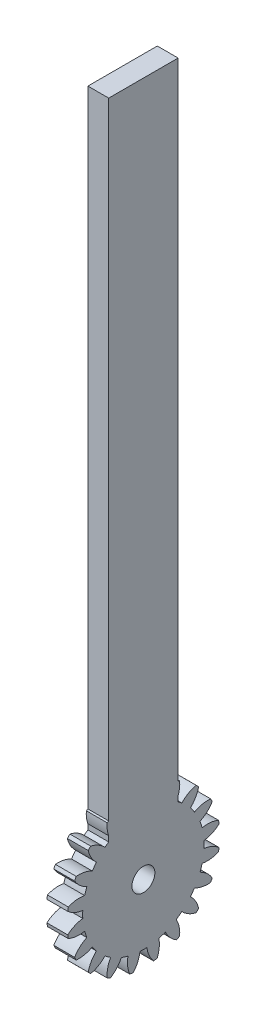
SolidWorks part; units mm, degrees
ref_plane "Plane1" through (0, 0, 0) normal (0, 0, 1) x (1, 0, 0)
ref_plane "Plane2" through (0, 0, 0) normal (0, 1, 0) x (1, 0, 0)
ref_plane "Plane3" through (0, 0, 0) normal (1, 0, 0) x (0, 0, -1)
sketch "HoldingSke" plane through (0, 0, 0) normal (0, 1, 0) x (1, 0, 0)
  line L0 (0, 0) -> (0.9397, -0.342)
  line L1 (-15, 0) -> (100, 0) construction
  line L2 (0, 0) -> (-2.1039, 2.3779)
  line L3 (0, 0) -> (-11.863, 4.5341)
  line L4 (0, 0) -> (8.1152, 2.9537)
  line L5 (0, 0) -> (-46.8476, -17.4728)
  line L6 (0, 0) -> (-2.4869, -1.6779)
  line L7 (-2.1039, 2.3779) -> (8.6586, 51.2059)
  line L8 (-76.2, 54.61) -> (-75.3, 54.61)
  line L9 (-71.009, 38.7566) -> (-53.1078, 45.2721)
  line L10 (-76.2, 71.12) -> (104.1128, 71.12)
  line L11 (0, 0) -> (-3, 0)
  line L12 (-76.2, 101.6) -> (-76.162, 101.6)
  line L13 (24.9733, 27.94) -> (52.9518, 28.4284)
  line L14 (24.9733, 27.94) -> (24.9743, 27.94)
  line L15 (24.9733, 27.94) -> (100.4006, 29.5858)
  line L16 (-63.627, -1) -> (-12.827, -1)
  circle A0 centre (0, 0) radius 2.5
  circle A1 centre (0, 0) radius 8.749
  circle A2 centre (0, 0) radius 37.5
  circle A3 centre (0, 0) radius 2.5
  dimension "Num_teeth" = 20
  dimension "Pitch_radius" = 180.3128
  dimension "Width" = 3
  dimension "Thickness" = 3
sketch "BasProSke" plane through (0, 0, 0) normal (0, 1, 0) x (1, 0, 0)
  line L0 (-10, 0) -> (60, 0) construction
  line L1 (0, 0) -> (0, 11)
  line L2 (0, 0) -> (3, 0)
  line L3 (3, 0) -> (3, 11)
  line L4 (3, 11) -> (0, 11)
  dimension "Thickness" = 3
  dimension "Diameter" = 22
revolve "Base-Revolve" add sketch "BasProSke" angle 360 about L0
sketch "TooCutSke" plane through (0, 0, 0) normal (1, 0, 0) x (0, 0, -1)
  line L1 (0, 0) -> (0, 107) construction
  line L2 (0, 0) -> (-0.8511, 9.9637) construction
  line L3 (0, 0) -> (-3.1206, 19.7028) construction
  line L4 (-0.8511, 9.9637) -> (-1.5603, 9.8514) construction
  arc A0 (0.4999, 8.7347) -> (-0.4999, 8.7347) centre (0, 0) ccw
  arc A1 (1.4852, 10.9249) -> (-1.4852, 10.9249) centre (0, 0) ccw
  circle A2 centre (0, 0) radius 10 construction
  circle A3 centre (0, 0) radius 9.3969 construction
  arc A4 (-0.4999, 8.7347) -> (-1.4852, 10.9249) centre (-4.4722, 8.2645) ccw
  arc A5 (1.4852, 10.9249) -> (0.4999, 8.7347) centre (4.4722, 8.2645) ccw
extrude "ToothCut" cut sketch "TooCutSke" along normal through all
fillet "Breaks" [suppressed] radius 0.02 tangent propagation no
fillet "RootFillets" [suppressed] radius 0.251
pattern_circular "TeethCuts" count 20 every 18 about axis through (-10, 0, 0) along (1, 0, 0) of "ToothCut", "RootFillets", "Breaks"
sketch "HubNeaOneSke" plane through (0, 0, 0) normal (-1, 0, 0) x (0, 0, 1)
  circle A0 centre (0, 0) radius 8.749
  dimension "Diameter" = 17.498
extrude "HubNearOne" [suppressed] add sketch "HubNeaOneSke" along normal blind 47.0001
sketch "HubNeaBotSke" plane through (0, 0, 0) normal (-1, 0, 0) x (0, 0, 1)
  circle A0 centre (0, 0) radius 8.749
  dimension "Diameter" = 17.498
extrude "HubNearBoth" [suppressed] add sketch "HubNeaBotSke" along normal blind 23.5
ref_plane "FarPln" through (3, 0, 0) normal (1, 0, 0) x (0, 0, -1)
sketch "HubFarSke" plane through (3, 0, 0) normal (1, 0, 0) x (0, 0, -1)
  circle A0 centre (0, 0) radius 8.749
  dimension "Diameter" = 17.498
extrude "HubFar" [suppressed] add sketch "HubFarSke" along normal blind 23.5
sketch "BorSke" plane through (0, 0, 0) normal (1, 0, 0) x (0, 0, -1)
  circle A0 centre (0, 0) radius 2.5
  dimension "Diameter" = 5
extrude "Bore" cut sketch "BorSke" along normal mid plane 100.0001
sketch "KeySke" plane through (0, 0, 0) normal (1, 0, 0) x (0, 0, -1)
  line L0 (-1, 0) -> (-1, 3.4)
  line L1 (-1, 3.4) -> (1, 3.4)
  line L2 (1, 3.4) -> (1, 0)
  line L3 (0, 0) -> (0, 34) construction
  line L4 (-1, 0) -> (1, 0)
  dimension "Width" = 2
extrude "Keyway" [suppressed] cut sketch "KeySke" along normal mid plane 100.0001
pattern_circular "Keyway2" [suppressed] count 2 every 90 about axis through (-10, 0, 0) along (1, 0, 0) reverse direction yes
sketch "Sketch1" plane through (3, 0, 0) normal (1, 0, 0) x (0, 0, -1)
  line L1 (-5, 0) -> (5, 0)
  line L2 (-5, 0) -> (-5, 100)
  line L3 (-5, 100) -> (5, 100)
  line L4 (5, 0) -> (5, 100)
  dimension "D1" = 10
  dimension "D2" = 100
extrude "Boss-Extrude1" add sketch "Sketch1" against normal blind 3
sketch "Sketch5" plane through (3, 0, 0) normal (1, 0, 0) x (0, 0, -1)
  line L0 (-2.5, 0) -> (2.5, 0) construction
  line L1 (2.5, 0) -> (-2.5, 0)
  arc A0 (-2.5, 0) -> (2.5, 0) centre (0, 0) cw
extrude "Cut-Extrude2" cut sketch "Sketch5" against normal blind 3
sketch "Sketch6" plane through (3, 0, 0) normal (1, 0, 0) x (0, 0, -1)
  circle A0 centre (0, 0) radius 2.5
  circle A1 centre (0, 0) radius 1.65
extrude "Boss-Extrude2" add sketch "Sketch6" against normal blind 3
equation "' \"Module@HoldingSke\" = 6.35"
equation "' \"Num_teeth@HoldingSke\" = 12"
equation "' \"Ap@HoldingSke\" =  20"
equation "' \"Ap@HoldingSke\" = 20"
equation "' \"Width@HoldingSke\" = 0.5 * 25.4"
equation "' \"Hub_dia@HoldingSke\"= 1 * 25.4"
equation "' \"Hub_dia@HoldingSke\" = 1 * 25.4"
equation "' \"Overall_len@HoldingSke\" = 1.0 * 25.4"
equation "' \"Bore@HoldingSke\" = 0.75 * 25.4"
equation "' \"T_dim@HoldingSke\" = 0.1 * 25.4"
equation "' \"Width@KeySke\" = 0.25 * 25.4"
equation "' \"Show_teeth@HoldingSke\" = 13"
equation "' \"Backlash@HoldingSke\" = 0.009 * 25.4"
equation "' \"Addendum_fac@HoldingSke\" = 1.0"
equation "' \"Dedendum_fac@HoldingSke\" = 1.25"
equation "' \"Dedendum_add@HoldingSke\" = 0.00005 * 25.4"
equation "' \"Clearance_fac@HoldingSke\" = 0.25"
equation "\"Pitch@HoldingSke\" = 1 / \"Module@HoldingSke\""
equation "\"Overcut_dia@TooCutSke\" = (\"Num_teeth@HoldingSke\" + 2 * \"Addendum_fac@HoldingSke\") / \"Pitch@HoldingSke\" + 0.002 * 25.4"
equation "\"Pitch_dia@TooCutSke\" = \"Num_teeth@HoldingSke\" / \"Pitch@HoldingSke\""
equation "\"Base_dia@TooCutSke\" = \"Num_teeth@HoldingSke\" / \"Pitch@HoldingSke\" * cos((\"Ap@HoldingSke\"  * 3.14159265 / 180))"
equation "\"Root_dia@TooCutSke\" = (\"Num_teeth@HoldingSke\" + 2) / \"Pitch@HoldingSke\" - 2 * (\"Addendum_fac@HoldingSke\" + \"Dedendum_fac@HoldingSke\") / \"Pitch@HoldingSke\" - \"Dedendum_add@HoldingSke\" * 2"
equation "\"Half_ang@TooCutSke\" = 180 / \"Num_teeth@HoldingSke\""
equation "\"Half_CT@TooCutSke\" = \"Num_teeth@HoldingSke\" / \"Pitch@HoldingSke\" * sin((3.14159265 / 2 / \"Num_teeth@HoldingSke\")) / 2 - 7 * \"Backlash@HoldingSke\" / 4"
equation "\"Flank_rad@TooCutSke\" = \"Num_teeth@HoldingSke\" / \"Pitch@HoldingSke\" / 5"
equation "\"Radius@RootFillets\" = \"Clearance_fac@HoldingSke\" / \"Pitch@HoldingSke\" + \"Dedendum_add@HoldingSke\""
equation "\"Break_rad@Breaks\" = 0.02 / \"Pitch@HoldingSke\""
equation "\"Thickness@HoldingSke\" = \"Width@HoldingSke\""
equation "\"OAL@HoldingSke\" = \"Thickness@HoldingSke\""
equation "\"MHD@HoldingSke\" = (\"Num_teeth@HoldingSke\" + 2) / \"Pitch@HoldingSke\" - 2 * (\"Addendum_fac@HoldingSke\" + \"Dedendum_fac@HoldingSke\")  / \"Pitch@HoldingSke\" - \"Dedendum_add@HoldingSke\" * 2"
equation "\"MBD@HoldingSke\" = (\"Num_teeth@HoldingSke\" + 2) / \"Pitch@HoldingSke\" - 2 * (\"Addendum_fac@HoldingSke\" + \"Dedendum_fac@HoldingSke\")  / \"Pitch@HoldingSke\" - \"Dedendum_add@HoldingSke\" * 2 - 0.002 * 25.4"
equation "\"MHD@HoldingSke\" = ((sgn( \"MHD@HoldingSke\" - \"Hub_dia@HoldingSke\" )-1)*( \"MHD@HoldingSke\" - \"Hub_dia@HoldingSke\" ))/-2+ \"Hub_dia@HoldingSke\""
equation "\"MBD@HoldingSke\" = ((sgn( \"MBD@HoldingSke\" - \"Bore@HoldingSke\" )-1)*( \"MBD@HoldingSke\" - \"Bore@HoldingSke\" ))/-2+ \"Bore@HoldingSke\""
equation "\"OAL@HoldingSke\" = ((sgn( \"OAL@HoldingSke\" - \"Overall_len@HoldingSke\" )+1)*( \"OAL@HoldingSke\" - \"Overall_len@HoldingSke\" ))/2 + \"Overall_len@HoldingSke\" + 0.000002 * 25.4"
equation "\"Num_teeth@TeethCuts\" = int( \"Show_teeth@HoldingSke\" ) + 1"
equation "\"Num_teeth@TeethCuts\" = ((sgn( \"Num_teeth@TeethCuts\" - \"Num_teeth@HoldingSke\" )-1)*( \"Num_teeth@TeethCuts\" - \"Num_teeth@HoldingSke\" ))/-2+ \"Num_teeth@HoldingSke\""
equation "\"Num_teeth@TeethCuts\" = ((sgn( \"Num_teeth@TeethCuts\" - 2.0)+1)*( \"Num_teeth@TeethCuts\" - 2.0))/2 +2.0"
equation "\"Angle@TeethCuts\" = 360.0 / \"Num_teeth@HoldingSke\""
equation "\"Diameter@BasProSke\" = (\"Num_teeth@HoldingSke\" + 2 * \"Addendum_fac@HoldingSke\") / \"Pitch@HoldingSke\""
equation "\"Thickness@BasProSke\"  = \"Thickness@HoldingSke\""
equation "' \"Fillet_rad@BasProSke\" =  \"Thickness@HoldingSke\" * 0.05"
equation "' \"Fillet_rad@BasProSke\" = \"Thickness@HoldingSke\" * 0.05"
equation "\"MHD@HoldingSke\" = ((sgn( \"MHD@HoldingSke\" - \"Root_dia@TooCutSke\" )-1)*( \"MHD@HoldingSke\" - \"Root_dia@TooCutSke\" ))/-2+ \"Root_dia@TooCutSke\""
equation "\"Diameter@HubNeaOneSke\" = \"MHD@HoldingSke\""
equation "\"Length@HubNearOne\" = \"OAL@HoldingSke\" - \"Thickness@BasProSke\""
equation "\"Diameter@HubNeaBotSke\" = \"MHD@HoldingSke\""
equation "\"Length@HubNearBoth\" = ( \"OAL@HoldingSke\" - \"Thickness@BasProSke\" ) / 2.0"
equation "\"Thickness@FarPln\" = \"Thickness@BasProSke\""
equation "\"Diameter@HubFarSke\" = \"MHD@HoldingSke\""
equation "\"Length@HubFar\" = ( \"OAL@HoldingSke\" - \"Thickness@BasProSke\" ) / 2.0"
equation "\"Diameter@BorSke\" = \"MBD@HoldingSke\""
equation "\"D1@Bore\" = \"OAL@HoldingSke\" * 2.0"
equation "\"D1@Keyway\" = \"OAL@HoldingSke\" * 2.0"
equation "\"Offset@KeySke\" = \"T_dim@HoldingSke\" + \"MBD@HoldingSke\" / 2.0"
